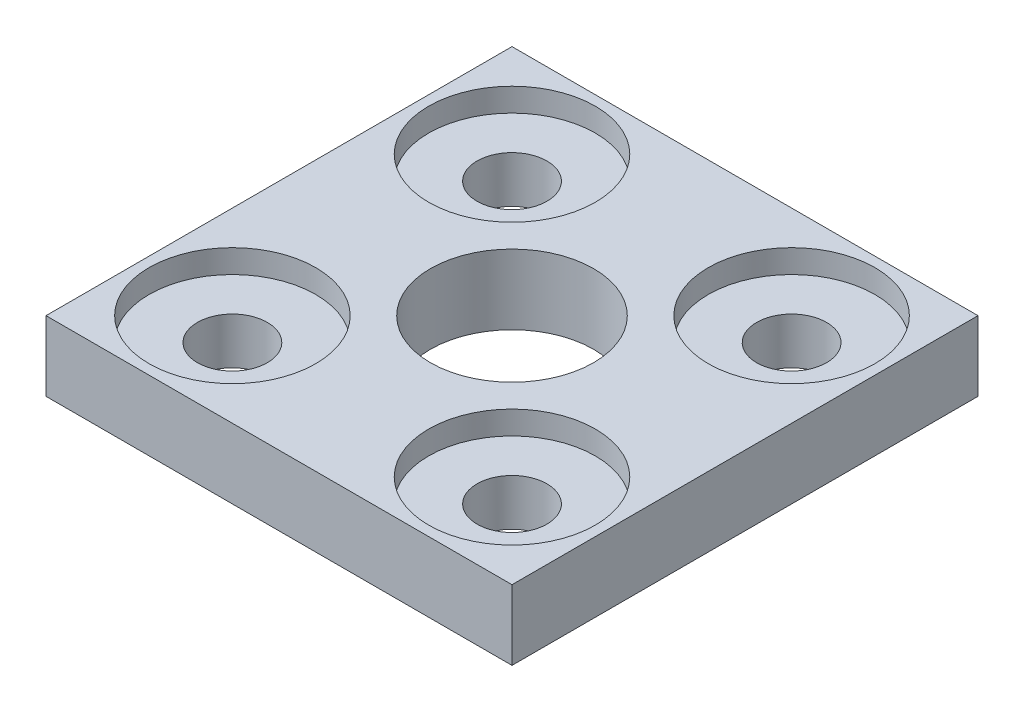
SolidWorks part; units mm, degrees
ref_plane "Front Plane" through (0, 0, 0) normal (0, 0, 1) x (1, 0, 0)
ref_plane "Top Plane" through (0, 0, 0) normal (0, 1, 0) x (1, 0, 0)
ref_plane "Right Plane" through (0, 0, 0) normal (1, 0, 0) x (0, 0, -1)
sketch "Sketch1" plane through (0, 0, 0) normal (0, 1, 0) x (1, 0, 0)
  line L0 (4, 16) -> (16, 16) construction
  line L1 (0, 0) -> (20, 0)
  line L2 (0, 0) -> (0, 20)
  line L3 (0, 20) -> (20, 20)
  line L4 (20, 0) -> (20, 20)
  line L5 (16, 4) -> (16, 16) construction
  line L6 (4, 4) -> (16, 4) construction
  line L7 (4, 4) -> (4, 16) construction
  line L8 (16, 16) -> (4, 4) construction
  circle A0 centre (16, 16) radius 1.5
  circle A1 centre (4, 16) radius 1.5
  circle A2 centre (4, 4) radius 1.5
  circle A3 centre (16, 4) radius 1.5
  circle A4 centre (10, 10) radius 3.5
  dimension "D3" = 3
  dimension "D4" = 7
  dimension "D1" = 20
  dimension "D2" = 4
extrude "Boss-Extrude1" add sketch "Sketch1" along normal blind 3
sketch "Sketch2" plane through (0, 3, 0) normal (0, 1, 0) x (1, 0, 0)
  line L0 (10, 20) -> (10, 0) construction
  line L1 (20, 20) -> (0, 20) construction
  line L2 (0, 0) -> (20, 0) construction
  line L3 (20, 10) -> (0, 10) construction
  line L4 (20, 0) -> (20, 20) construction
  line L5 (0, 20) -> (0, 0) construction
  circle A0 centre (16, 16) radius 3.575
  circle A1 centre (4, 16) radius 3.575
  circle A2 centre (16, 4) radius 3.575
  circle A3 centre (4, 4) radius 3.575
  dimension "D1" = 7.15
extrude "Cut-Extrude1" cut sketch "Sketch2" against normal blind 1
